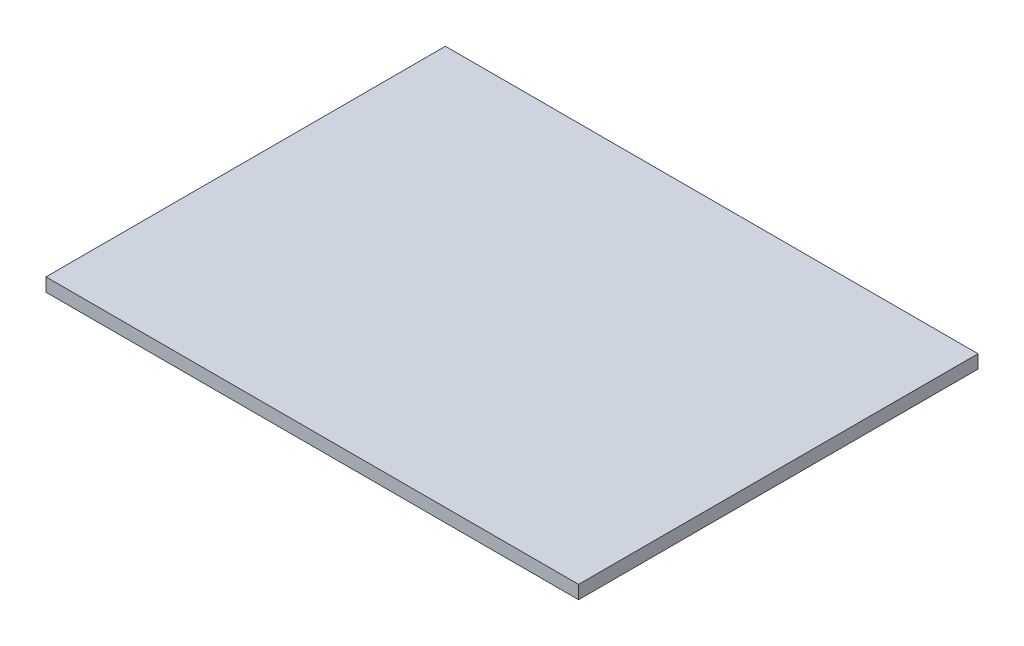
SolidWorks part; units mm, degrees
ref_plane "Alzado" through (0, 0, 0) normal (0, 0, 1) x (1, 0, 0)
ref_plane "Planta" through (0, 0, 0) normal (0, 1, 0) x (1, 0, 0)
ref_plane "Vista lateral" through (0, 0, 0) normal (1, 0, 0) x (0, 0, -1)
sketch "Croquis1" plane through (0, 0, 0) normal (0, 1, 0) x (1, 0, 0)
  line L1 (-20, 15) -> (20, 15)
  line L2 (-20, 15) -> (-20, -15)
  line L3 (-20, -15) -> (20, -15)
  line L4 (20, 15) -> (20, -15)
  line L5 (-20, 15) -> (20, -15) construction
  line L6 (-20, -15) -> (20, 15) construction
  point P0 (0, 0)
  dimension "D1" = 30
  dimension "D2" = 40
extrude "Saliente-Extruir1" add sketch "Croquis1" along normal blind 1
